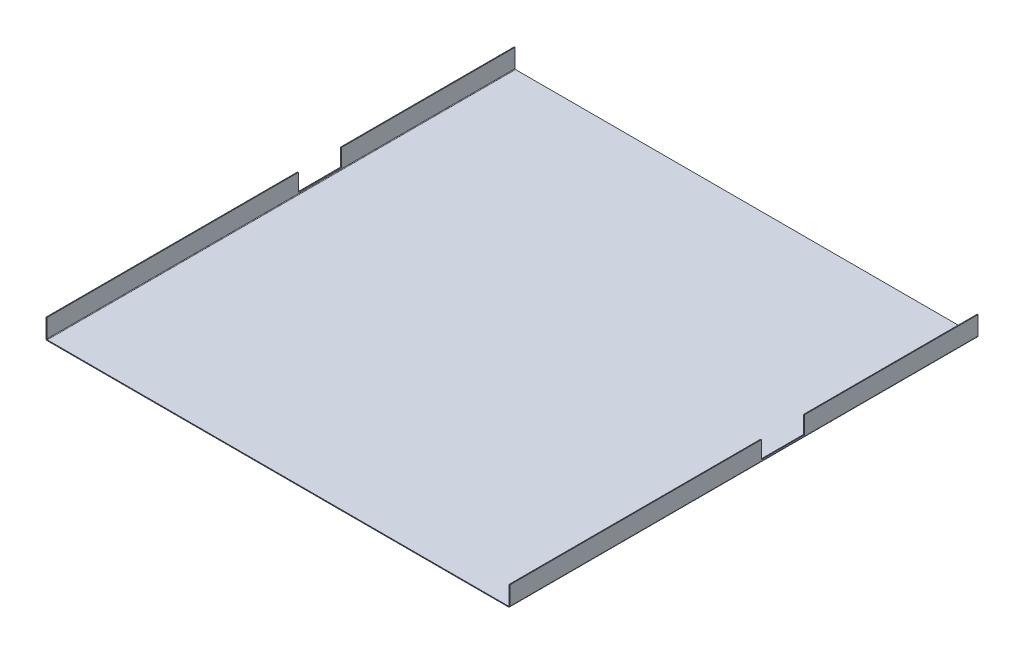
SolidWorks part; units mm, degrees
note: The reader was unsure of these and kept them because the rebuilt part matched: flange length of "Edge-Flange1".
ref_plane "Front Plane" through (0, 0, 0) normal (0, 0, 1) x (1, 0, 0)
ref_plane "Top Plane" through (0, 0, 0) normal (0, 1, 0) x (1, 0, 0)
ref_plane "Right Plane" through (0, 0, 0) normal (1, 0, 0) x (0, 0, -1)
sketch "Sketch2" plane through (0, 0, 0) normal (0, 1, 0) x (1, 0, 0)
  line L1 (0, 0) -> (590.8, 0)
  line L2 (0, 0) -> (0, 600)
  line L3 (0, 600) -> (590.8, 600)
  line L4 (590.8, 0) -> (590.8, 600)
  dimension "D1" = 600
  dimension "D2" = 590.8
base flange "Base-Flange1" sketch "Sketch2" thickness 1.016 reverse thickness direction no parameters "D1"=0.7366
edge flange "Edge-Flange1" sketch "Sketch11" flange profiles "Sketch11", "Sketch12" flange angle 90 flange length 25.396 flange position bend outside bend radius 0.7366 thickness 1.016 relief rectangular parameters "D6"=10, "D8"=1
sketch "Sketch11" plane through (0, 0, 0) normal (-1, 0, 0) x (0, 0, 1)
  line L2 (-600, 0) -> (-600, 24.38)
  line L3 (-600, 24.38) -> (0, 24.38)
  line L4 (0, 24.38) -> (0, 0)
  line L7 (-600, 0) -> (0, 0) construction
  line L8 (-600, 0) -> (0, 0)
  dimension "D1" = 24.38
sketch "Sketch12" plane through (590.8, 0, 0) normal (1, 0, 0) x (0, 0, -1)
  line L2 (0, 0) -> (0, 24.38)
  line L3 (0, 24.38) -> (600, 24.38)
  line L4 (600, 24.38) -> (600, 0)
  line L7 (0, 0) -> (600, 0) construction
  line L8 (0, 0) -> (600, 0)
  dimension "D1" = 24.38
bend "EdgeBend1" bend radius 0.7366 bend angle 90 parameters "D5"=1
bend "EdgeBend2" bend radius 0.7366 bend angle 90 parameters "D5"=2
sketch "Sketch31" plane through (-1.7526, 0, 0) normal (-1, 0, 0) x (0, 0, 1)
  line L0 (0, 24.38) -> (-600, 24.38) construction
  line L1 (-377.65, 24.38) -> (-322.35, 24.38)
  line L2 (-377.65, 24.38) -> (-377.65, 2.154)
  line L3 (-377.65, 2.154) -> (-322.35, 2.154)
  line L4 (-322.35, 24.38) -> (-322.35, 2.154)
  line L5 (-600, 24.38) -> (-600, 0.7366) construction
  line L6 (0, -1.016) -> (-600, -1.016) construction
  dimension "D1" = 222.35
  dimension "D2" = 55.3
  dimension "D3" = 3.17
extrude "Cut-Extrude1" cut sketch "Sketch31" against normal through all both and the other way through all normal cut yes
sketch "Bend-Lines1" [suppressed] plane through (0, 0, 0) normal (0, 1, 0) x (1, 0, 0)
sketch "Bounding-Box1" [suppressed] plane through (0, 0, 0) normal (0, 1, 0) x (1, 0, 0)
sheet metal parameters "Sheet-Metal1" thickness 1.016 parameters "D1"=0.7366
flat pattern "Flat-Pattern1" [suppressed]
sketch "Bend-Lines2" plane through (0, 0, 0) normal (0, 1, 0) x (1, 0, 0)
sketch3d "Bounding-Box2" [suppressed]
  line L0 (0, 0, 0) -> (0, 600, 0) construction
  line L1 (590.8, 0, 0) -> (590.8, 600, 0) construction
  line L2 (0, 0, 0) -> (590.8, 0, 0) construction
  line L3 (0, 600, 0) -> (590.8, 600, 0) construction
sheet metal parameters "Sheet-Metal2" thickness 1.016 parameters "D1"=0.7366
flat pattern "Flat-Pattern1"
sketch "Bend-Lines2" plane through (0, 0, 0) normal (0, 1, 0) x (1, 0, 0)
  line L0 (591.0409, 0) -> (591.0409, 600) construction
  line L1 (-0.2409, 600) -> (-0.2409, 0) construction
  line L2 (591.0409, 0) -> (591.0409, 600) construction
  line L3 (-0.2409, 600) -> (-0.2409, 0) construction
sketch3d "Bounding-Box2" [suppressed]
  line L0 (615.6618, 600, 0) -> (-24.8618, 600, 0) construction
  line L1 (615.6618, 0, 0) -> (-24.8618, 0, 0) construction
  line L2 (615.6618, 600, 0) -> (615.6618, 0, 0) construction
  line L3 (-24.8618, 600, 0) -> (-24.8618, 0, 0) construction
bend of the flat pattern "Flatten-<EdgeBend1>1"
bend of the flat pattern "Flatten-<EdgeBend2>1"
sheet metal parameters "Sheet-Metal4" thickness 1.016 parameters "D1"=0.7366
flat pattern "Flat-Pattern1"
sketch "Bend-Lines2" plane through (0, 0, 0) normal (0, 1, 0) x (1, 0, 0)
  line L0 (591.7775, 0) -> (591.7775, 600) construction
  line L1 (-0.9775, 600) -> (-0.9775, 0) construction
  line L2 (591.7775, 0) -> (591.7775, 600) construction
  line L3 (-0.9775, 600) -> (-0.9775, 0) construction
sketch3d "Bounding-Box2" [suppressed]
  line L0 (616.3984, 600, 0) -> (-25.5984, 600, 0) construction
  line L1 (616.3984, 0, 0) -> (-25.5984, 0, 0) construction
  line L2 (616.3984, 600, 0) -> (616.3984, 0, 0) construction
  line L3 (-25.5984, 600, 0) -> (-25.5984, 0, 0) construction
bend of the flat pattern "Flatten-<EdgeBend1>1"
bend of the flat pattern "Flatten-<EdgeBend2>1"
